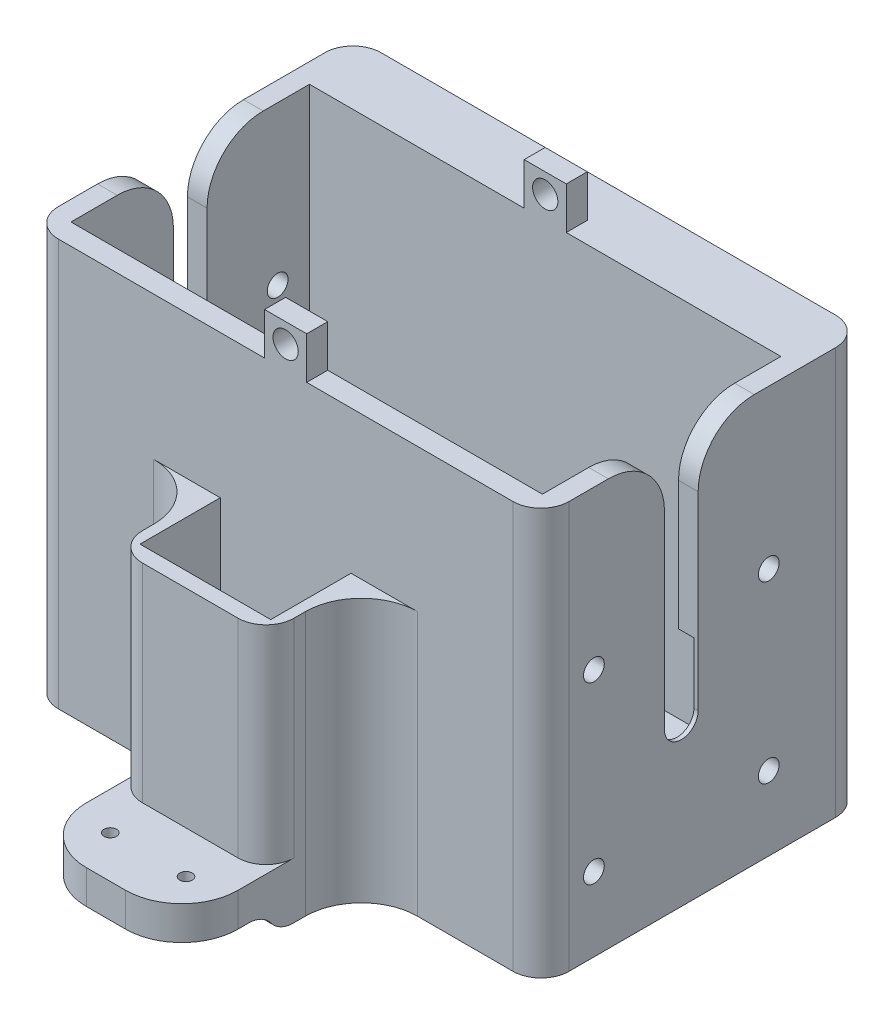
SolidWorks part; units mm, degrees
ref_plane "Plan de face" through (0, 0, 0) normal (0, 0, 1) x (1, 0, 0)
ref_plane "Plan de dessus" through (0, 0, 0) normal (0, 1, 0) x (1, 0, 0)
ref_plane "Plan de droite" through (0, 0, 0) normal (1, 0, 0) x (0, 0, -1)
sketch "Esquisse1" plane through (0, 0, 0) normal (1, 0, 0) x (0, 0, -1)
  line L2 (-15.8423, 13.6674) -> (-15.8423, -28.8326)
  line L3 (-15.8423, -28.8326) -> (26.6577, -28.8326)
  line L4 (26.6577, 13.6674) -> (26.6577, -28.8326)
  line L7 (-19.5923, -36.3326) -> (30.4077, -36.3326)
  line L10 (-19.5923, 13.6674) -> (-19.5923, -36.3326)
  line L11 (30.4077, 13.6674) -> (30.4077, -36.3326)
  line L12 (-15.8423, 13.6674) -> (-15.8423, 36.1674)
  line L13 (-19.5923, 13.6674) -> (-19.5923, 36.1674)
  line L14 (-19.5923, 36.1674) -> (-15.8423, 36.1674)
  line L15 (30.4077, 13.6674) -> (30.4077, 36.1674)
  line L16 (30.4077, 36.1674) -> (26.6577, 36.1674)
  line L17 (26.6577, 36.1674) -> (26.6577, 13.6674)
  dimension "D1" = 42.5
  dimension "D2" = 42.5
  dimension "D3" = 22.5
extrude "Boss.-Extru.1" add sketch "Esquisse1" along normal blind 84
sketch "Esquisse6" plane through (0, 0, 19.5923) normal (0, 0, 1) x (1, 0, 0)
  line L3 (28.5, 10.6674) -> (55.5, 10.6674)
  line L4 (28.5, 10.6674) -> (28.5, -36.3326)
  line L5 (28.5, -36.3326) -> (55.5, -36.3326)
  line L6 (55.5, 10.6674) -> (55.5, -36.3326)
  dimension "D3" = 27
  dimension "D4" = 47
extrude "Boss.-Extru.3" add sketch "Esquisse6" along normal blind 17
sketch "Esquisse7" plane through (0, 10.6674, 0) normal (0, 1, 0) x (1, 0, 0)
  line L0 (55.5, -19.5923) -> (28.5, -19.5923) construction
  line L2 (30.35, -19.5923) -> (53.65, -19.5923)
  line L3 (30.35, -19.5923) -> (30.35, -33.8923)
  line L4 (30.35, -33.8923) -> (53.65, -33.8923)
  line L5 (53.65, -19.5923) -> (53.65, -33.8923)
  line L6 (55.5, -36.5923) -> (55.5, -19.5923) construction
  dimension "D1" = 14.3
  dimension "D2" = 23.3
  dimension "D3" = 1.85
  dimension "D4" = 0
extrude "Enlèv. mat.-Extru.4" cut sketch "Esquisse7" against normal blind 43.3
sketch "Esquisse8" plane through (84, 0, 0) normal (1, 0, 0) x (0, 0, -1)
  line L3 (-19.5923, -36.3326) -> (30.4077, -36.3326)
  line L4 (-10.1673, 7.9924) -> (20.9827, -23.1576) construction
  line L5 (-10.1673, -23.1576) -> (20.9827, -23.1576) construction
  line L6 (-10.1673, -23.1576) -> (-10.1673, 7.9924) construction
  line L7 (-10.1673, 7.9924) -> (20.9827, 7.9924) construction
  line L8 (20.9827, -23.1576) -> (20.9827, 7.9924) construction
  line L9 (-10.1673, -23.1576) -> (20.9827, 7.9924) construction
  line L10 (-19.5923, 13.6674) -> (-19.5923, -36.3326)
  line L11 (30.4077, 13.6674) -> (30.4077, -36.3326)
  line L12 (-15.8423, -28.8326) -> (26.6577, -28.8326) construction
  line L13 (5.4077, -28.8326) -> (5.4077, -7.5826) construction
  line L14 (2.4077, -7.5826) -> (2.4077, 13.6674)
  line L15 (8.4077, -7.5826) -> (8.4077, 13.6674)
  line L17 (-19.5923, 36.1674) -> (2.4077, 36.1674)
  line L18 (2.4077, 36.1674) -> (2.4077, 13.6674)
  line L19 (-19.5923, 36.1674) -> (-19.5923, 13.6674)
  line L20 (30.4077, 13.6674) -> (30.4077, 36.1674)
  line L21 (30.4077, 36.1674) -> (8.4077, 36.1674)
  line L22 (8.4077, 36.1674) -> (8.4077, 13.6674)
  arc A0 (2.4077, -7.5826) -> (8.4077, -7.5826) centre (5.4077, -7.5826) ccw
  circle A1 centre (-10.1673, 7.9924) radius 1.85
  circle A2 centre (20.9827, 7.9924) radius 1.85
  circle A3 centre (20.9827, -23.1576) radius 1.85
  circle A4 centre (-10.1673, -23.1576) radius 1.85
  point P18 (5.4077, -7.5826)
  dimension "D1" = 21.25
extrude "Boss.-Extru.4" add sketch "Esquisse8" along normal blind 3.5
sketch "Esquisse12" plane through (84, 0, 0) normal (-1, 0, 0) x (0, 0, 1)
  circle A0 centre (-5.4077, -7.5826) radius 11.25
  dimension "D1" = 22.5
extrude "Enlèv. mat.-Extru.7" cut sketch "Esquisse12" against normal blind 2.75
ref_plane "Plan1" through (42, 0, 0) normal (-1, 0, 0) x (0, 0, 1)
mirror "Symétrie1" about plane through (42, 0, 0) normal (-1, 0, 0) of "Boss.-Extru.4", "Enlèv. mat.-Extru.7"
sketch "Esquisse13" plane through (0, 0, 36.5923) normal (0, 0, 1) x (1, 0, 0)
  line L0 (28.5, 10.6674) -> (28.5, -36.3326) construction
  line L1 (55.5, -36.3326) -> (28.5, -36.3326)
  line L2 (55.5, -36.3326) -> (55.5, -26.3326)
  line L3 (55.5, -26.3326) -> (28.5, -26.3326)
  line L4 (28.5, -36.3326) -> (28.5, -26.3326)
  dimension "D1" = 10
extrude "Boss.-Extru.5" add sketch "Esquisse13" along normal blind 15
sketch "Esquisse15" plane through (0, -36.3326, 0) normal (0, -1, 0) x (1, 0, 0)
  line L0 (55.5, 51.5923) -> (55.5, 19.5923) construction
  line L1 (28.5, 51.5923) -> (55.5, 51.5923)
  line L2 (28.5, 51.5923) -> (28.5, 36.5923)
  line L3 (28.5, 36.5923) -> (55.5, 36.5923)
  line L4 (55.5, 51.5923) -> (55.5, 36.5923)
  dimension "D1" = 15
extrude "Enlèv. mat.-Extru.9" cut sketch "Esquisse15" against normal blind 4
sketch "Esquisse14" plane through (0, -36.3326, 0) normal (0, -1, 0) x (1, 0, 0)
  line L4 (28.5, 36.5923) -> (55.5, 36.5923) construction
  line L5 (55.5, 36.5923) -> (55.5, 19.5923) construction
  circle A0 centre (35.25, 44.0923) radius 1.11
  circle A1 centre (48.75, 44.0923) radius 1.11
  point P3 (42, 44.0923)
  point P14 (42, 44.0923)
  dimension "D1" = 13.5
extrude "Enlèv. mat.-Extru.8" cut sketch "Esquisse14" against normal blind 15
fillet "Congé6" radius 5 1 edges at (42, -36.3326, 36.5923)
fillet "Congé7" radius 5 1 edges at (42, -32.3326, 36.5923)
fillet "Congé1" radius 10 2 edges at (28.5, -29.3326, 51.5923) (55.5, -29.3326, 51.5923)
fillet "Congé2" radius 10 4 edges at (85.75, 36.1674, -2.4077) (85.75, 36.1674, -8.4077) (-1.75, 36.1674, -2.4077) (-1.75, 36.1674, -8.4077)
fillet "Congé3" radius 10 2 edges at (55.5, -12.8326, 19.5923) (28.5, -12.8326, 19.5923)
fillet "Congé4" radius 5 2 edges at (-3.5, -0.0826, 19.5923) (87.5, -0.0826, 19.5923)
fillet "Congé8" radius 5 2 edges at (55.5, -7.8326, 36.5923) (28.5, -7.8326, 36.5923)
sketch "Esquisse16" plane through (0, 36.1674, 0) normal (0, 1, 0) x (1, 0, 0)
  line L5 (30.35, -19.5923) -> (53.65, -19.5923) construction
  line L6 (39.5, -15.8423) -> (44.5, -15.8423)
  line L8 (39.5, -19.5923) -> (44.5, -19.5923)
  line L10 (30.35, -19.5923) -> (30.35, -15.8423) construction
  line L11 (84, -15.8423) -> (0, -15.8423) construction
  line L12 (-3.5, 5.4077) -> (87.5, 5.4077) construction
  line L13 (-3.5, 8.4077) -> (-3.5, 2.4077) construction
  line L14 (87.5, 2.4077) -> (87.5, 8.4077) construction
  line L19 (39.5, 26.6577) -> (38.25, 26.6577)
  line L20 (39.5, -15.8423) -> (38.25, -15.8423)
  line L22 (39.5, -19.5923) -> (38.25, -19.5923)
  line L23 (38.25, -15.8423) -> (38.25, -19.5923)
  line L24 (44.5, -15.8423) -> (45.75, -15.8423)
  line L26 (44.5, -19.5923) -> (45.75, -19.5923)
  line L27 (45.75, -15.8423) -> (45.75, -19.5923)
  line L28 (38.25, 26.6577) -> (38.25, 30.4077)
  line L29 (39.5, 30.4077) -> (38.25, 30.4077)
  line L30 (39.5, 30.4077) -> (44.5, 30.4077)
  line L31 (44.5, 30.4077) -> (45.75, 30.4077)
  line L32 (45.75, 26.6577) -> (45.75, 30.4077)
  line L33 (44.5, 26.6577) -> (45.75, 26.6577)
  line L34 (39.5, 26.6577) -> (44.5, 26.6577)
  dimension "D1" = 5
  dimension "D3" = 1.25
  dimension "D4" = 1.25
extrude "Boss.-Extru.6" add sketch "Esquisse16" along normal blind 7.5 from surface starting at face at (42, 36.1674, 13.2494)
sketch "Esquisse17" plane through (0, 0, 19.5923) normal (0, 0, 1) x (1, 0, 0)
  line L0 (42, 43.6674) -> (42, 13.6114) construction
  line L1 (38.25, 43.6674) -> (45.75, 43.6674) construction
  circle A0 centre (42, 40.1674) radius 2.25
  dimension "D1" = 4.5
  dimension "D2" = 3.5
extrude "Enlèv. mat.-Extru.10" cut sketch "Esquisse17" against normal through all
sketch "Esquisse20" plane through (0, 0, -30.4077) normal (0, 0, -1) x (-1, 0, 0)
  line L1 (-87.5, 36.1674) -> (3.5, 36.1674)
  line L2 (-87.5, 36.1674) -> (-87.5, -36.3326)
  line L3 (-87.5, -36.3326) -> (3.5, -36.3326)
  line L4 (3.5, 36.1674) -> (3.5, -36.3326)
extrude "Boss.-Extru.7" add sketch "Esquisse20" along normal blind 7.5
sketch "Esquisse21" plane through (0, 0, -37.9077) normal (0, 0, -1) x (-1, 0, 0)
  line L1 (-75.9479, 27.2574) -> (-0.5592, 27.2574) construction
  line L10 (-87.5, 36.1674) -> (-87.5, -36.3326) construction
  line L11 (-87.5, -36.3326) -> (3.5, -36.3326) construction
  line L15 (3.5, 36.1674) -> (-87.5, 36.1674) construction
  circle A7 centre (-75.9479, 27.2574) radius 1.7
  circle A8 centre (-75.9479, -27.4181) radius 1.7
  circle A9 centre (-9.6679, -27.1626) radius 1.7
  dimension "D1" = 54.6755
  dimension "D2" = 8.91
extrude "Enlèv. mat.-Extru.11" cut sketch "Esquisse21" against normal blind 5 contours A8 | A9 | A7 region at (75.9479, -27.4181, -37.9077) region at (9.6679, -27.1626, -37.9077)
fillet "Congé9" radius 5 2 edges at (-3.5, -0.0826, -37.9077) (87.5, -0.0826, -37.9077)
